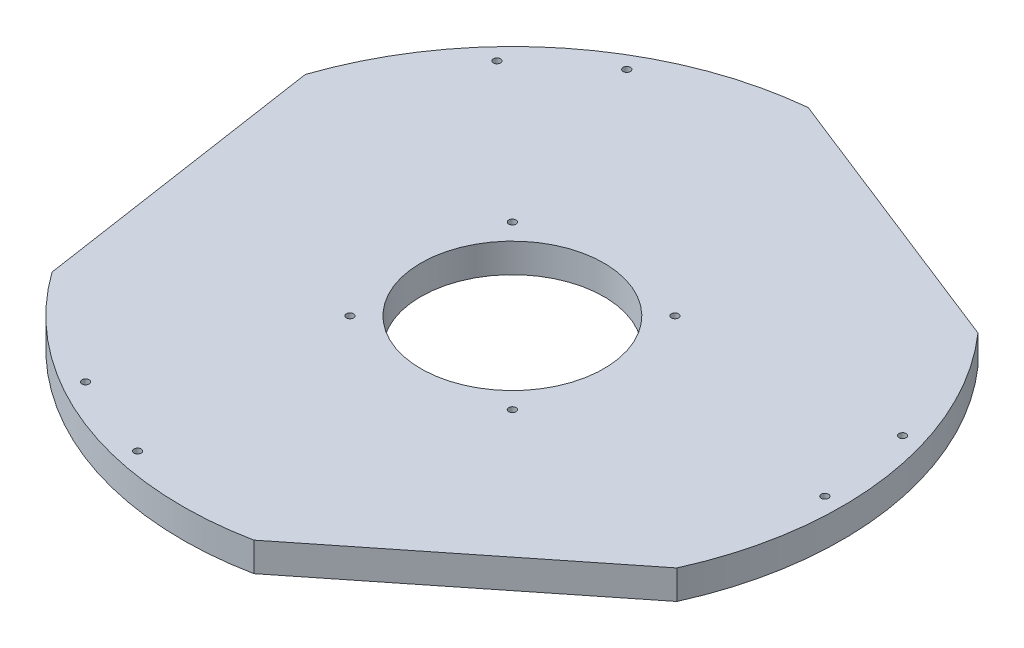
SolidWorks part; units mm, degrees
material "Oak"
ref_plane "Front Plane" through (0, 0, 0) normal (0, 0, 1) x (1, 0, 0)
ref_plane "Top Plane" through (0, 0, 0) normal (0, 1, 0) x (1, 0, 0)
ref_plane "Right Plane" through (0, 0, 0) normal (1, 0, 0) x (0, 0, -1)
sketch "Sketch1" plane through (0, 0, 0) normal (0, 0, 1) x (1, 0, 0)
  line L0 (0, -200000) -> (0, 218797.9879) construction
  line L1 (144.145, -24.4122) -> (144.145, -37.1122) construction
  line L2 (0, -24.4122) -> (144.145, -24.4122) construction
  line L3 (144.145, -37.1122) -> (0, -37.1122) construction
  line L4 (0, -200000) -> (0, 218797.9879) construction
  line L5 (144.145, -24.4122) -> (144.145, -37.1122)
  line L6 (0, -24.4122) -> (144.145, -24.4122)
  line L7 (144.145, -37.1122) -> (0, -37.1122)
  line L8 (0, -24.4122) -> (0, -37.1122)
revolve "Revolve1" add sketch "Sketch1" angle 360 about L4
hole_wizard "1/8 (0.125) Diameter Hole1" positions "Sketch2" profile "Sketch3" hole size "1/8" standard "ANSI Inch" end condition up to next
sketch "Sketch2" plane through (0, -24.4122, 0) normal (0, 1, 0) x (1, 0, 0)
  line L0 (0, 0) -> (136.525, 0) construction
  line L3 (0, 0) -> (-68.2625, -118.2341) construction
  line L6 (0, 0) -> (-68.2625, 118.2341) construction
  line L7 (-99.8481, 93.1098) -> (0, 0) construction
  line L9 (0, 0) -> (-30.7114, -133.0259) construction
  line L12 (0, 0) -> (130.5595, 39.916) construction
  line L14 (-35.5, -35.5) -> (35.5, -35.5) construction
  line L15 (-35.5, -35.5) -> (-35.5, 35.5) construction
  line L16 (-35.5, 35.5) -> (35.5, 35.5) construction
  line L17 (35.5, -35.5) -> (35.5, 35.5) construction
  line L18 (-35.5, 0) -> (0, 0) construction
  line L19 (0, 0) -> (0, -35.5) construction
  circle A0 centre (0, 0) radius 136.525
  point P0 (136.525, 0)
  point P2 (-68.2625, -118.2341)
  point P4 (-68.2625, 118.2341)
  point P32 (-99.8481, 93.1098)
  point P57 (130.5595, 39.916)
  point P60 (-30.7114, -133.0259)
  point P138 (-35.5, -35.5)
  point P141 (-35.5, 35.5)
  point P144 (35.5, 35.5)
  point P147 (35.5, -35.5)
  dimension "D3" = 17
  dimension "D1" = 120
  dimension "D2" = 120
  dimension "D4" = 120
  dimension "D5" = 120
  dimension "D6" = 71
sketch "Sketch3" plane through (136.525, -24.4122, 0) normal (1, 0, 0) x (0, 0, 1)
  line L0 (0, 0) -> (0, 12.7)
  line L1 (0, 12.7) -> (1.5875, 12.7)
  line L2 (1.5875, 12.7) -> (1.5875, 0)
  line L5 (1.5875, 0) -> (0, 0)
  line L11 (0, -6.35) -> (0, 107.95) construction
  dimension "Thru Hole Dia." = 3.175
  dimension "Thru Hole Depth" = 12.7
sketch "Sketch4" plane through (0, -24.4122, 0) normal (0, 1, 0) x (1, 0, 0)
  line L0 (253.7221, 37.919) -> (-94.0222, -238.6893)
  line L1 (-94.0222, -238.6893) -> (-159.6999, 200.7703)
  line L2 (-159.6999, 200.7703) -> (253.7221, 37.919)
  line L3 (253.7221, 37.919) -> (0, 0) construction
  line L4 (130.5595, 39.916) -> (136.525, 0) construction
  circle A0 centre (0, 0) radius 128.27 construction
  point P6 (133.5423, 19.958)
  dimension "D1" = 256.54
extrude "Cut-Extrude1" cut sketch "Sketch4" against normal through all flip side to cut
sketch "Sketch6" plane through (0, -24.4122, 0) normal (0, 1, 0) x (1, 0, 0)
  circle A0 centre (0, 0) radius 40
  dimension "D1" = 80
extrude "Cut-Extrude2" cut sketch "Sketch6" against normal through all
